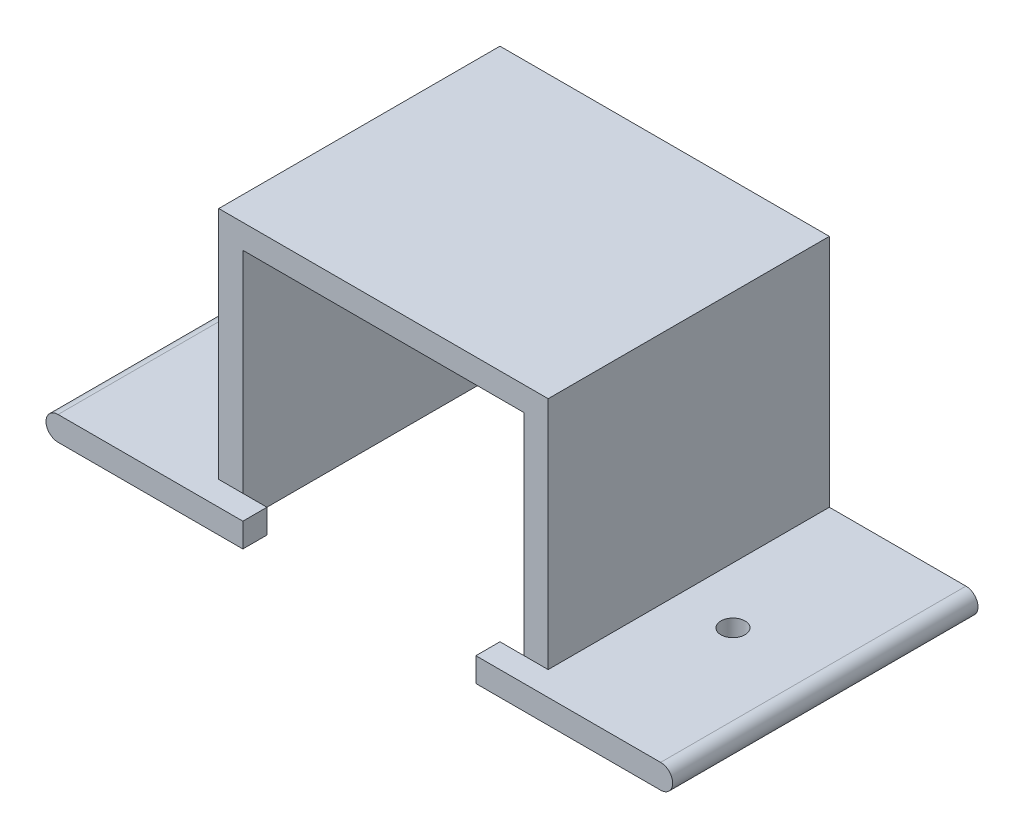
SolidWorks part; units mm, degrees
ref_plane "Front Plane" through (0, 0, 0) normal (0, 0, 1) x (1, 0, 0)
ref_plane "Top Plane" through (0, 0, 0) normal (0, 1, 0) x (1, 0, 0)
ref_plane "Right Plane" through (0, 0, 0) normal (1, 0, 0) x (0, 0, -1)
sketch "Sketch1" plane through (0, 0, 0) normal (0, 0, 1) x (1, 0, 0)
  line L0 (0, 0) -> (-20, 0)
  line L1 (-20, 0) -> (-20, 27.2)
  line L3 (-55, 27.2) -> (-55, 0)
  line L4 (-55, 0) -> (-75, 0)
  line L5 (0, 3) -> (-17, 3)
  line L6 (-17, 3) -> (-17, 30.2)
  line L8 (-58, 30.2) -> (-58, 3)
  line L9 (-58, 3) -> (-75, 3)
  line L10 (-20, 27.2) -> (-20, 29.2)
  line L11 (-20, 29.2) -> (-55, 29.2)
  line L12 (-55, 29.2) -> (-55, 27.2)
  line L13 (-17, 30.2) -> (-17, 32.2)
  line L14 (-20, 27.2) -> (-55, 27.2) construction
  line L15 (-17, 32.2) -> (-58, 32.2)
  line L16 (-58, 32.2) -> (-58, 30.2)
  line L17 (-17, 30.2) -> (-58, 30.2) construction
  arc A0 (0, 0) -> (0, 3) centre (0, 1.5) ccw
  arc A1 (-75, 0) -> (-75, 3) centre (-75, 1.5) cw
  dimension "D1" = 3
extrude "Boss-Extrude1" add sketch "Sketch1" along normal blind 32
sketch "Sketch2" plane through (0, 0, 0) normal (0, 0, -1) x (-1, 0, 0)
  line L0 (75, 0) -> (55, 0)
  line L1 (75, 0) -> (55, 0)
  line L2 (55, 0) -> (55, 29.2)
  line L6 (20, 29.2) -> (20, 0)
  line L8 (20, 0) -> (0, 0)
  line L9 (20, 0) -> (0, 0)
  line L10 (0, 3) -> (17, 3)
  line L11 (0, 3) -> (17, 3)
  line L12 (17, 3) -> (17, 32.2)
  line L13 (17, 3) -> (17, 32.2)
  line L14 (17, 32.2) -> (58, 32.2)
  line L16 (58, 32.2) -> (58, 3)
  line L17 (58, 32.2) -> (58, 3)
  line L18 (58, 3) -> (75, 3)
  line L19 (58, 3) -> (75, 3)
  line L20 (55, 0) -> (20, 0)
  line L23 (55, 29.2) -> (20, 29.2)
  line L28 (17, 32.2) -> (58, 32.2)
  arc A0 (0, 3) -> (0, 0) centre (0, 1.5) ccw
  arc A1 (0, 3) -> (0, 0) centre (0, 1.5) ccw
  arc A2 (75, 0) -> (75, 3) centre (75, 1.5) ccw
  arc A3 (75, 0) -> (75, 3) centre (75, 1.5) ccw
extrude "Boss-Extrude2" add sketch "Sketch2" along normal blind 3
sketch "Sketch3" plane through (0, 0, 32) normal (0, 0, 1) x (1, 0, 0)
  line L4 (-20, 0) -> (-23, 0)
  line L5 (-23, 0) -> (-23, 3)
  line L6 (-23, 3) -> (-20, 3)
  line L9 (-20, 3) -> (0, 3)
  line L10 (0, 3) -> (-17, 3) construction
  line L11 (-20, 0) -> (0, 0)
  line L12 (-20, 8.4579) -> (-55, 8.4579) construction
  line L13 (-55, 0) -> (-55, 29.2) construction
  line L14 (-37.5, 8.4579) -> (-37.5, -0.8521) construction
  line L15 (-55, 0) -> (-75, 0)
  line L16 (-55, 3) -> (-75, 3)
  line L17 (-52, 3) -> (-55, 3)
  line L18 (-52, 0) -> (-52, 3)
  line L19 (-55, 0) -> (-52, 0)
  arc A0 (0, 0) -> (0, 3) centre (0, 1.5) ccw
  arc A1 (-75, 0) -> (-75, 3) centre (-75, 1.5) cw
extrude "Boss-Extrude3" add sketch "Sketch3" along normal blind 3
sketch "Sketch4" plane through (0, 0, 0) normal (0, -1, 0) x (1, 0, 0)
  line L0 (-55, 16) -> (-75, 16) construction
  line L1 (-55, 32) -> (-55, 0) construction
  line L2 (-75, 35) -> (-75, -3) construction
  line L3 (-55, 16) -> (-20, 16) construction
  line L4 (-20, 32) -> (-20, 0) construction
  line L5 (-20, 16) -> (-37.5, 16) construction
  line L6 (-37.5, 16) -> (-37.5, 23.8364) construction
  circle A0 centre (-65, 16) radius 1.5
  circle A1 centre (-10, 16) radius 1.5
extrude "Cut-Extrude1" cut sketch "Sketch4" against normal blind 4
